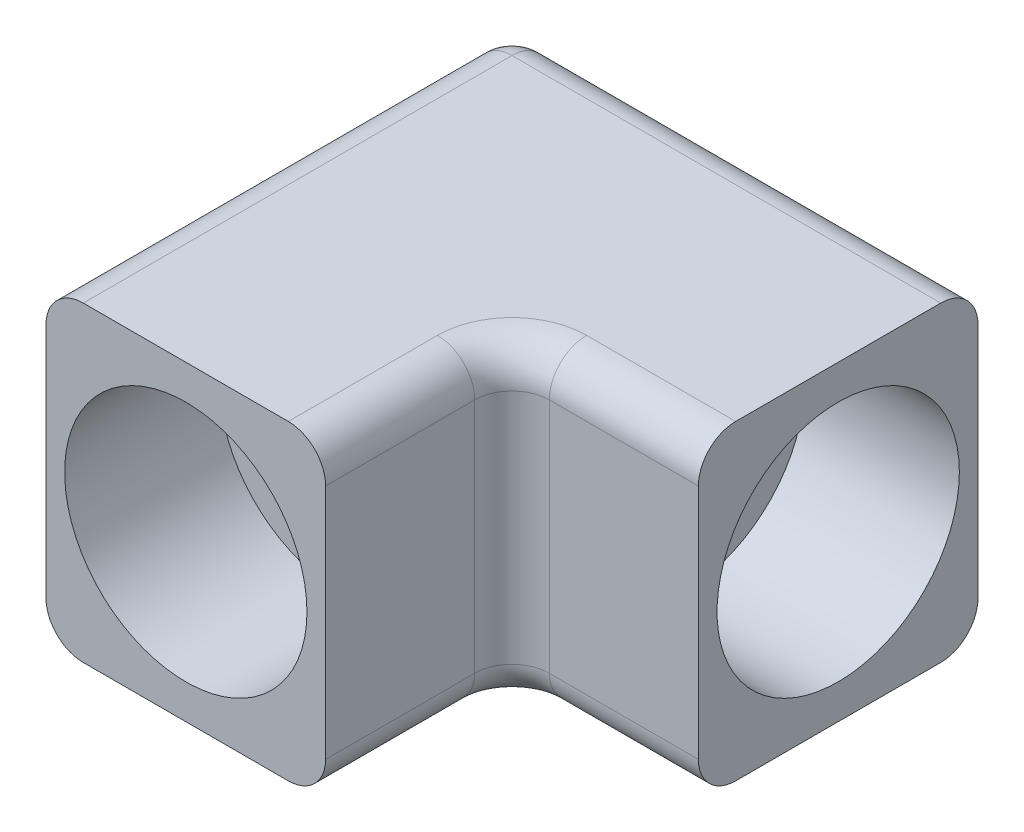
SolidWorks part; units mm, degrees
ref_plane "Front Plane" through (0, 0, 0) normal (0, 0, 1) x (1, 0, 0)
ref_plane "Top Plane" through (0, 0, 0) normal (0, 1, 0) x (1, 0, 0)
ref_plane "Right Plane" through (0, 0, 0) normal (1, 0, 0) x (0, 0, -1)
sketch "Sketch1" plane through (0, 0, 0) normal (0, 1, 0) x (1, 0, 0)
  line L1 (7.5, -5) -> (-7.5, -5)
  line L2 (7.5, -5) -> (7.5, 5)
  line L3 (7.5, 5) -> (-7.5, 5)
  line L4 (-7.5, -5) -> (-7.5, 5)
  line L5 (7.5, -5) -> (-7.5, 5) construction
  line L6 (7.5, 5) -> (-7.5, -5) construction
  line L8 (-7.5, 5) -> (-7.5, 20)
  line L9 (-7.5, 20) -> (7.5, 20)
  line L10 (7.5, 5) -> (7.5, 20)
  line L11 (7.5, 5) -> (17.5, 5)
  line L13 (7.5, 20) -> (17.5, 20)
  line L14 (17.5, 5) -> (17.5, 20)
  point P0 (0, 0)
  dimension "D1" = 10
  dimension "D2" = 15
  dimension "D3" = 15
  dimension "D4" = 10
extrude "Boss-Extrude1" add sketch "Sketch1" along normal blind 16.7 contours L4 L1 L2 L3 | L3 L10 L9 L8 | L11 L14 L13 L10 region at (0, 0, 0) region at (0, 0, -12.5) region at (12.5, 0, -12.5)
sketch "Sketch2" plane through (0, 0, 5) normal (0, 0, 1) x (1, 0, 0)
  line L0 (0, 0) -> (0, 16.7) construction
  line L1 (7.5, 0) -> (-7.5, 0) construction
  line L2 (7.5, 16.7) -> (-7.5, 16.7) construction
  circle A0 centre (0, 8.35) radius 6.5
  dimension "D1" = 13
extrude "Cut-Extrude1" cut sketch "Sketch2" against normal offset from surface (8.3 mm away) 16.7 up to face at (5, 8.35, -20)
sketch "Sketch3" plane through (17.5, 0, 0) normal (1, 0, 0) x (0, 0, -1)
  line L0 (12.5, 0) -> (12.5, 16.7) construction
  line L1 (5, 0) -> (20, 0) construction
  line L2 (5, 16.7) -> (20, 16.7) construction
  circle A0 centre (12.5, 8.35) radius 6.5
  dimension "D1" = 13
extrude "Cut-Extrude2" cut sketch "Sketch3" against normal offset from surface (8.3 mm away) 16.7 up to face at (-7.5, 8.35, -7.5)
sketch "Sketch4" plane through (0, 0, 0) normal (0, -1, 0) x (1, 0, 0)
  line L0 (0, 5) -> (0, -20) construction
  line L1 (7.5, 5) -> (-7.5, 5) construction
  line L2 (-7.5, -20) -> (17.5, -20) construction
  line L3 (17.5, -12.5) -> (-7.5, -12.5) construction
  line L4 (17.5, -5) -> (17.5, -20) construction
  line L5 (-7.5, 5) -> (-7.5, -20) construction
  circle A0 centre (0, -12.5) radius 6.5
  dimension "D1" = 13
extrude "Cut-Extrude3" cut sketch "Sketch4" against normal offset from surface (14.7 mm away) 2 up to face at (5.8333, 16.7, -6.6667)
fillet "Fillet8" radius 2 10 edges at (-7.5, 8.35, -20) (7.5, 8.35, -5) (-7.5, 0, -7.5) (-7.5, 16.7, -7.5) (12.5, 16.7, -5) (7.5, 16.7, 0) (7.5, 0, 0) (12.5, 0, -5) (5, 16.7, -20) (5, 0, -20)
